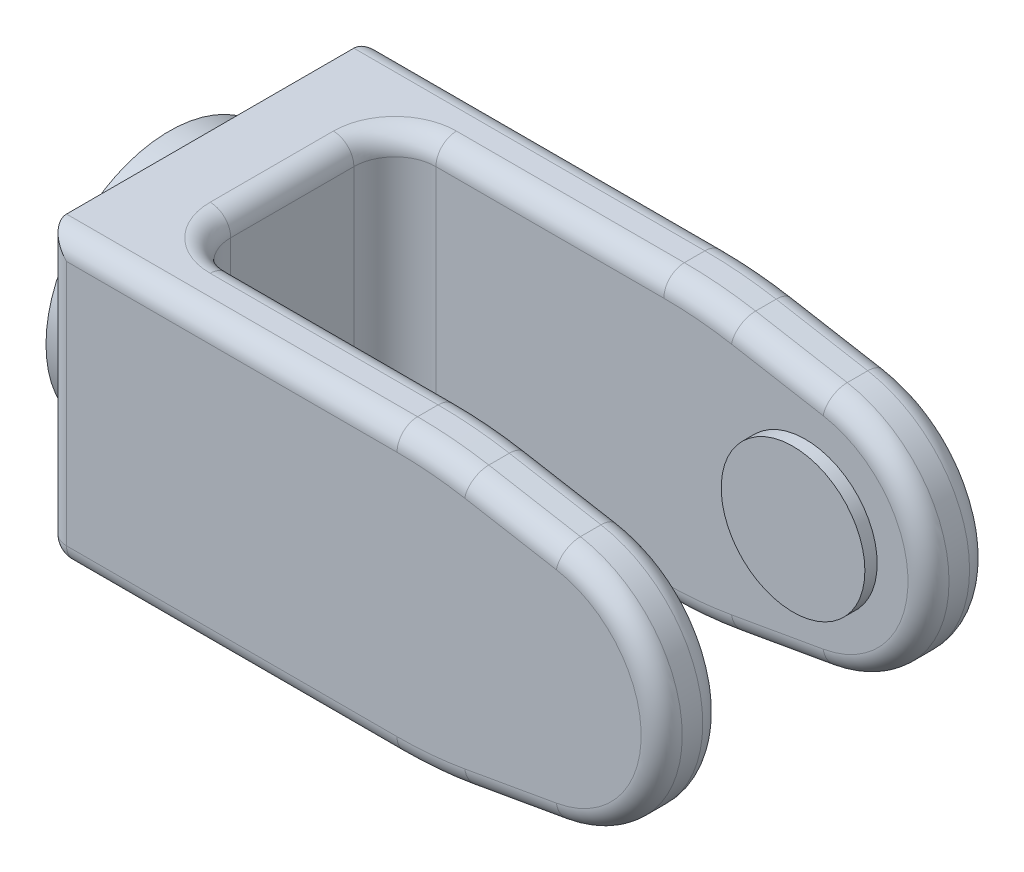
SolidWorks part; units mm, degrees
ref_plane "Front Plane" through (0, 0, 0) normal (0, 0, 1) x (1, 0, 0)
ref_plane "Top Plane" through (0, 0, 0) normal (0, 1, 0) x (1, 0, 0)
ref_plane "Right Plane" through (0, 0, 0) normal (1, 0, 0) x (0, 0, -1)
sketch "Sketch1" plane through (0, 0, 0) normal (0, 0, 1) x (1, 0, 0)
  line L0 (0, 0) -> (94.2683, 0)
  line L1 (94.2683, 0) -> (125.2094, 5.4558)
  line L2 (125.2094, 64.5442) -> (94.2683, 70)
  line L3 (94.2683, 70) -> (0, 70)
  line L4 (0, 70) -> (0, 0)
  arc A0 (125.2094, 5.4558) -> (125.2094, 64.5442) centre (120, 35) ccw
  dimension "D2" = 30
  dimension "D1" = 70
  dimension "D3" = 170
  dimension "D4" = 170
  dimension "D5" = 120
extrude "Boss-Extrude1" add sketch "Sketch1" along normal mid plane 80
sketch "Sketch2" plane through (0, 0, 0) normal (0, 1, 0) x (1, 0, 0)
  line L0 (94.2683, -40) -> (0, -40) construction
  line L1 (20, 25) -> (200, 25)
  line L2 (20, 25) -> (20, -25)
  line L3 (20, -25) -> (200, -25)
  line L4 (200, 25) -> (200, -25)
  line L5 (94.2683, 40) -> (0, 40) construction
  line L6 (0, -40) -> (0, 40) construction
  dimension "D1" = 15
  dimension "D2" = 15
  dimension "D3" = 20
  dimension "D4" = 180
extrude "Cut-Extrude1" cut sketch "Sketch2" along normal through all
sketch "Sketch3" plane through (0, 0, -25) normal (0, 0, 1) x (1, 0, 0)
  circle A0 centre (120, 35) radius 17.5
  dimension "D1" = 35
extrude "Boss-Extrude3" add sketch "Sketch3" along normal blind 3
mirror "Mirror1" about plane through (0, 0, 0) normal (0, 0, 1) of "Boss-Extrude3"
sketch "Sketch4" plane through (0, 0, 0) normal (-1, 0, 0) x (0, 0, 1)
  line L0 (-40, 70) -> (-40, 0) construction
  circle A0 centre (0, 35) radius 30
  point P6 (-40, 35)
  dimension "D1" = 60
extrude "Boss-Extrude4" add sketch "Sketch4" along normal blind 10
sketch "Sketch5" plane through (-10, 0, 0) normal (-1, 0, 0) x (0, 0, 1)
  circle A0 centre (0, 35) radius 25
  dimension "D1" = 50
extrude "Boss-Extrude5" add sketch "Sketch5" along normal blind 3
fillet "Fillet2" radius 100 4 edges at (94.2683, 70, -32.5) (94.2683, 70, 32.5) (94.2683, 0, -32.5) (94.2683, 0, 32.5)
fillet "Fillet3" radius 10 2 edges at (20, 35, 25) (20, 35, -25)
fillet "Fillet4" radius 5 37 edges at (94.235, 0.3805, -25) (114.0468, 3.4875, -25) (150, 35, -25) (114.0468, 66.5125, -25) (94.235, 69.6195, -25) (57.7597, 70, -25) (22.9289, 70, -22.0711) (20, 70, 0) (22.9289, 70, 22.0711) (57.7597, 70, 25) (94.235, 69.6195, 25) (114.0468, 66.5125, 25) (150, 35, 25) (114.0468, 3.4875, 25) (94.235, 0.3805, 25) (0, 35, -40) (94.235, 0.3805, -40) (114.0468, 3.4875, -40) (150, 35, -40) (114.0468, 66.5125, -40) (94.235, 69.6195, -40) (42.7597, 70, -40) (150, 35, 40) (114.0468, 3.4875, 40) (94.235, 0.3805, 40) (0, 35, 40) (42.7597, 70, 40) (94.235, 69.6195, 40) (114.0468, 66.5125, 40) (0, 0, 0) (42.7597, 0, 40) (57.7597, 0, 25) (22.9289, 0, 22.0711) (20, 0, 0) (22.9289, 0, -22.0711) (57.7597, 0, -25) (42.7597, 0, -40)
